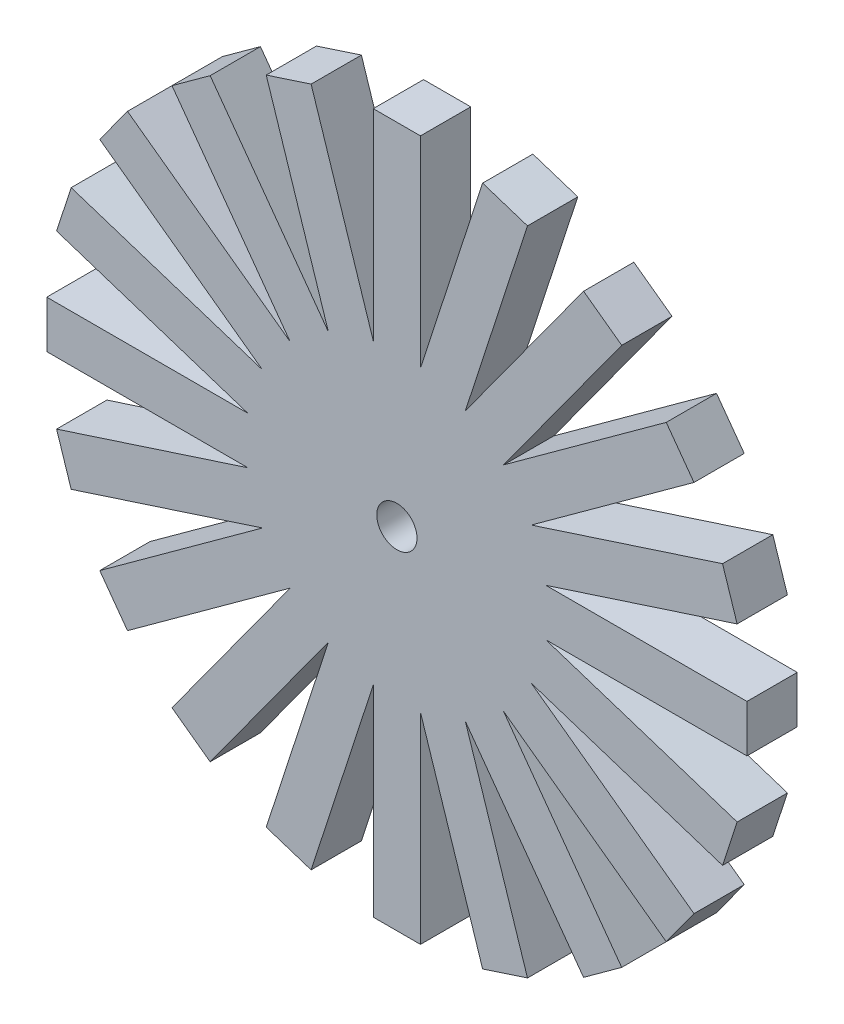
SolidWorks part; units mm, degrees
ref_plane "Plan de face" through (0, 0, 0) normal (0, 0, 1) x (1, 0, 0)
ref_plane "Plan de dessus" through (0, 0, 0) normal (0, 1, 0) x (1, 0, 0)
ref_plane "Plan de droite" through (0, 0, 0) normal (1, 0, 0) x (0, 0, -1)
sketch "Esquisse1" plane through (0, 0, 0) normal (0, 0, 1) x (1, 0, 0)
  line L0 (0, 15) -> (0, -15) construction
  line L1 (-15, 0) -> (15, 0) construction
  line L2 (-14.8153, -2.3465) -> (-34.8153, -2.3465)
  line L3 (-34.8153, -2.3465) -> (-34.8153, 2.3465)
  line L4 (-14.8153, 2.3465) -> (-34.8153, 2.3465)
  line L5 (0, 0) -> (-14.8153, 2.3465) construction
  line L6 (-13.3651, 6.8099) -> (-32.3862, 12.9902)
  line L7 (-33.8365, 8.5269) -> (-32.3862, 12.9902)
  line L8 (-14.8153, 2.3465) -> (-33.8365, 8.5269)
  line L9 (-10.6066, 10.6066) -> (-26.7869, 22.3623)
  line L10 (-29.5454, 18.5656) -> (-26.7869, 22.3623)
  line L11 (-13.3651, 6.8099) -> (-29.5454, 18.5656)
  line L12 (-6.8099, 13.3651) -> (-18.5656, 29.5454)
  line L13 (-22.3623, 26.7869) -> (-18.5656, 29.5454)
  line L14 (-10.6066, 10.6066) -> (-22.3623, 26.7869)
  line L15 (-2.3465, 14.8153) -> (-8.5269, 33.8365)
  line L16 (-12.9902, 32.3862) -> (-8.5269, 33.8365)
  line L17 (-6.8099, 13.3651) -> (-12.9902, 32.3862)
  line L18 (2.3465, 14.8153) -> (2.3465, 34.8153)
  line L19 (-2.3465, 34.8153) -> (2.3465, 34.8153)
  line L20 (-2.3465, 14.8153) -> (-2.3465, 34.8153)
  line L21 (6.8099, 13.3651) -> (12.9902, 32.3862)
  line L22 (8.5269, 33.8365) -> (12.9902, 32.3862)
  line L23 (2.3465, 14.8153) -> (8.5269, 33.8365)
  line L24 (10.6066, 10.6066) -> (22.3623, 26.7869)
  line L25 (18.5656, 29.5454) -> (22.3623, 26.7869)
  line L26 (6.8099, 13.3651) -> (18.5656, 29.5454)
  line L27 (13.3651, 6.8099) -> (29.5454, 18.5656)
  line L28 (26.7869, 22.3623) -> (29.5454, 18.5656)
  line L29 (10.6066, 10.6066) -> (26.7869, 22.3623)
  line L30 (14.8153, 2.3465) -> (33.8365, 8.5269)
  line L31 (32.3862, 12.9902) -> (33.8365, 8.5269)
  line L32 (13.3651, 6.8099) -> (32.3862, 12.9902)
  line L33 (14.8153, -2.3465) -> (34.8153, -2.3465)
  line L34 (34.8153, 2.3465) -> (34.8153, -2.3465)
  line L35 (14.8153, 2.3465) -> (34.8153, 2.3465)
  line L36 (13.3651, -6.8099) -> (32.3862, -12.9902)
  line L37 (33.8365, -8.5269) -> (32.3862, -12.9902)
  line L38 (14.8153, -2.3465) -> (33.8365, -8.5269)
  line L39 (10.6066, -10.6066) -> (26.7869, -22.3623)
  line L40 (29.5454, -18.5656) -> (26.7869, -22.3623)
  line L41 (13.3651, -6.8099) -> (29.5454, -18.5656)
  line L42 (6.8099, -13.3651) -> (18.5656, -29.5454)
  line L43 (22.3623, -26.7869) -> (18.5656, -29.5454)
  line L44 (10.6066, -10.6066) -> (22.3623, -26.7869)
  line L45 (2.3465, -14.8153) -> (8.5269, -33.8365)
  line L46 (12.9902, -32.3862) -> (8.5269, -33.8365)
  line L47 (6.8099, -13.3651) -> (12.9902, -32.3862)
  line L48 (-2.3465, -14.8153) -> (-2.3465, -34.8153)
  line L49 (2.3465, -34.8153) -> (-2.3465, -34.8153)
  line L50 (2.3465, -14.8153) -> (2.3465, -34.8153)
  line L51 (-6.8099, -13.3651) -> (-12.9902, -32.3862)
  line L52 (-8.5269, -33.8365) -> (-12.9902, -32.3862)
  line L53 (-2.3465, -14.8153) -> (-8.5269, -33.8365)
  line L54 (-10.6066, -10.6066) -> (-22.3623, -26.7869)
  line L55 (-18.5656, -29.5454) -> (-22.3623, -26.7869)
  line L56 (-6.8099, -13.3651) -> (-18.5656, -29.5454)
  line L57 (-13.3651, -6.8099) -> (-29.5454, -18.5656)
  line L58 (-26.7869, -22.3623) -> (-29.5454, -18.5656)
  line L59 (-10.6066, -10.6066) -> (-26.7869, -22.3623)
  line L60 (-14.8153, -2.3465) -> (-33.8365, -8.5269)
  line L61 (-32.3862, -12.9902) -> (-33.8365, -8.5269)
  line L62 (-13.3651, -6.8099) -> (-32.3862, -12.9902)
  circle A0 centre (0, 0) radius 15
  circle A1 centre (0, 0) radius 2
  point P12 (-34.8153, 0)
  dimension "D1" = 30
  dimension "D5" = 4
  dimension "D2" = 9
  dimension "D3" = 20
  dimension "D4" = 20
extrude "Boss.-Extru.1" add sketch "Esquisse1" along normal blind 5 contours A0 L4 L3 L2 | A0 | A0 | A0 | A0 | A0 | A0 | A0 | A0 | A0 | A0 | A0 L6 L7 L8 | A0 L60 L61 L62 | A0 L54 L55 L56 | A0 L48 L49 L50 | A0 L42 L43 L44 | A0 L36 L37 L38 | A0 L30 L31 L32 | A0 L24 L25 L26 | A0 L18 L19 L20 | A0 L12 L13 L14 region at (-23.6593, -7.6874, 0) region at (-24.8769, 0, 0) region at (-14.5757, 0, 0) region at (-23.6593, 7.6874, 0) region at (-20.1258, -14.6223, 0) region at (-20.1258, 14.6223, 0) region at (-14.6223, -20.1258, 0) region at (-14.6223, 20.1258, 0) region at (-7.6874, -23.6593, 0) region at (-7.6874, 23.6593, 0) region at (0, -24.8769, 0) region at (0, 24.8769, 0) region at (7.6874, -23.6593, 0) region at (7.6874, 23.6593, 0) region at (14.6223, -20.1258, 0) region at (14.6223, 20.1258, 0) region at (20.1258, -14.6223, 0) region at (20.1258, 14.6223, 0) region at (23.6593, -7.6874, 0) region at (23.6593, 7.6874, 0) region at (24.8769, 0, 0)
